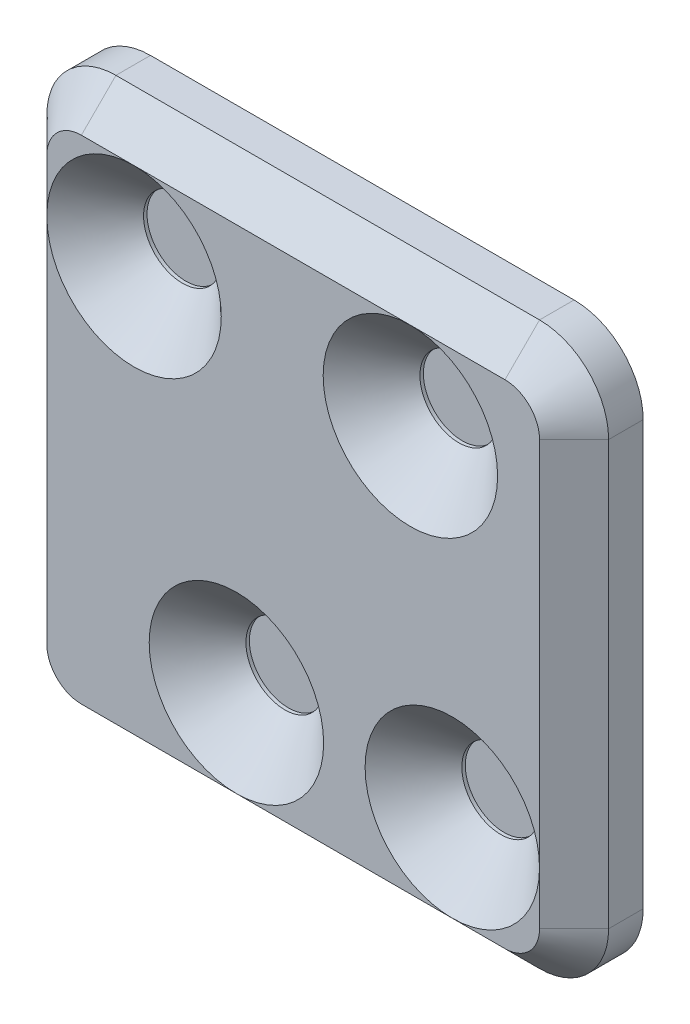
SolidWorks part; units mm, degrees
ref_plane "Front Plane" through (0, 0, 0) normal (0, 0, 1) x (1, 0, 0)
ref_plane "Top Plane" through (0, 0, 0) normal (0, 1, 0) x (1, 0, 0)
ref_plane "Right Plane" through (0, 0, 0) normal (1, 0, 0) x (0, 0, -1)
sketch "Sketch1" plane through (0, 0, 0) normal (0, 0, 1) x (1, 0, 0)
  line L1 (16.2635, -16.2635) -> (-16.2635, -16.2635)
  line L2 (16.2635, -16.2635) -> (16.2635, 16.2635)
  line L3 (16.2635, 16.2635) -> (-16.2635, 16.2635)
  line L4 (-16.2635, -16.2635) -> (-16.2635, 16.2635)
  line L5 (16.2635, -16.2635) -> (-16.2635, 16.2635) construction
  line L6 (16.2635, 16.2635) -> (-16.2635, -16.2635) construction
  point P0 (0, 0)
  dimension "D1" = 46
extrude "Boss-Extrude1" add sketch "Sketch1" along normal blind 4
fillet "Fillet1" radius 4 4 edges at (-16.2635, -16.2635, 2) (16.2635, -16.2635, 2) (16.2635, 16.2635, 2) (-16.2635, 16.2635, 2)
chamfer "Chamfer1" distance 2 angle 45 8 edges at (0, -16.2635, 4) (15.0919, -15.0919, 4) (-15.0919, -15.0919, 4) (16.2635, 0, 4) (-16.2635, 0, 4) (15.0919, 15.0919, 4) (-15.0919, 15.0919, 4) (0, 16.2635, 4)
sketch "Sketch2" plane through (0, 0, 4) normal (0, 0, 1) x (1, 0, 0)
  line L1 (9.2135, -9.2135) -> (-9.2135, -9.2135) construction
  line L2 (9.2135, -9.2135) -> (9.2135, 9.2135) construction
  line L3 (9.2135, 9.2135) -> (-9.2135, 9.2135) construction
  line L4 (-9.2135, -9.2135) -> (-9.2135, 9.2135) construction
  line L5 (9.2135, -9.2135) -> (-9.2135, 9.2135) construction
  line L6 (9.2135, 9.2135) -> (-9.2135, -9.2135) construction
  line L8 (12.2635, 14.2635) -> (-12.2635, 14.2635) construction
  circle A0 centre (-9.2135, 9.2135) radius 2.25
  circle A2 centre (9.2135, -9.2135) radius 2.25
  circle A5 centre (-3.2865, -9.2135) radius 2.25
  circle A7 centre (6.7865, 9.2135) radius 2.25
  point P0 (0, 0)
  dimension "D1" = 4.5
  dimension "D2" = 2.8
  dimension "D3" = 8
  dimension "D4" = 11.5
extrude "Cut-Extrude1" cut sketch "Sketch2" against normal blind 3
chamfer "Chamfer2" distance 2.8 angle 45 4 edges at (-1.0365, -9.2135, 4) (11.4635, -9.2135, 4) (-6.9635, 9.2135, 4) (9.0365, 9.2135, 4)
